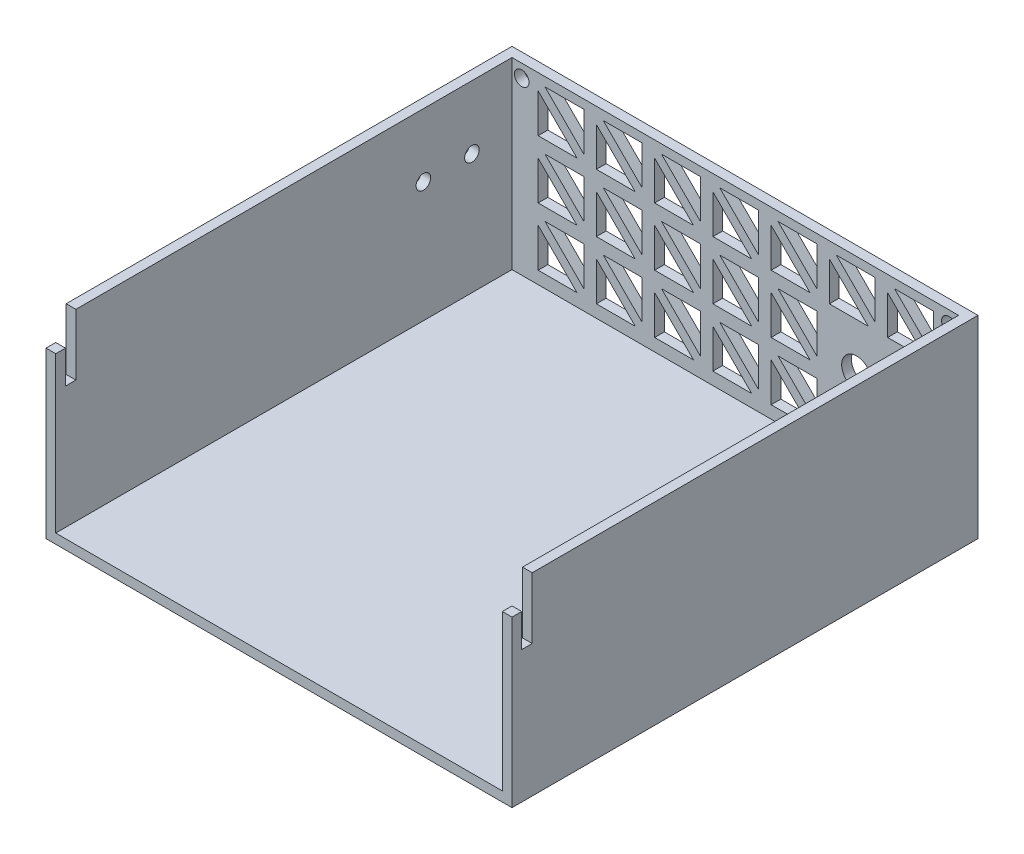
SolidWorks part; units mm, degrees
note: The reader was unsure of these and kept them because the rebuilt part matched: shared geometry of "Sketch7<2>".
ref_plane "Front Plane" through (0, 0, 0) normal (0, 0, 1) x (1, 0, 0)
ref_plane "Top Plane" through (0, 0, 0) normal (0, 1, 0) x (1, 0, 0)
ref_plane "Right Plane" through (0, 0, 0) normal (1, 0, 0) x (0, 0, -1)
sketch "Sketch1" plane through (0, 0, 0) normal (0, 1, 0) x (1, 0, 0)
  line L1 (0, 0) -> (152.4, 0)
  line L2 (0, 0) -> (0, 152.4)
  line L3 (0, 152.4) -> (152.4, 152.4)
  line L4 (152.4, 0) -> (152.4, 152.4)
  dimension "D1" = 152.4
  dimension "D2" = 152.4
extrude "Boss-Extrude1" add sketch "Sketch1" along normal blind 247.65
shell "Shell1" thickness 3.175 removed face at (76.2, 247.65, -76.2) removed face at (76.2, 123.825, 0)
ref_plane "Plane1" through (0, 0, -117.475) normal (0, 0, 1) x (1, 0, 0)
sketch "Sketch3" plane through (0, 0, -117.475) normal (0, 0, 1) x (1, 0, 0)
  line L1 (0, 66.675) -> (152.4, 66.675)
  line L2 (0, 66.675) -> (0, 70.1548)
  line L3 (0, 70.1548) -> (152.4, 70.1548)
  line L4 (152.4, 66.675) -> (152.4, 70.1548)
  line L5 (0, 240.8936) -> (152.4, 240.8936)
  line L6 (3.175, 3.175) -> (149.225, 3.175) construction
  line L8 (0, 195.5546) -> (152.4, 195.5546)
  line L9 (0, 195.5546) -> (0, 192.0748)
  line L10 (0, 192.0748) -> (152.4, 192.0748)
  line L11 (152.4, 195.5546) -> (152.4, 192.0748)
  line L12 (152.4, 247.65) -> (152.4, 0) construction
  line L13 (0, 247.65) -> (0, 0) construction
  line L14 (0, 240.8936) -> (0, 236.8296)
  line L15 (0, 236.8296) -> (152.4, 236.8296)
  line L16 (152.4, 240.8936) -> (152.4, 236.8296)
  dimension "D1" = 3.4798
  dimension "D2" = 63.5
  dimension "D3" = 121.92
  dimension "D4" = 41.275
  dimension "D5" = 4.064
extrude "Cut-Extrude1" cut sketch "Sketch3" along normal up to next
sketch "Sketch4" plane through (152.4, 0, 0) normal (1, 0, 0) x (0, 0, -1)
  line L0 (0, 240.8936) -> (117.475, 240.8936) construction
  line L1 (0, 247.65) -> (6.604, 247.65)
  line L2 (0, 247.65) -> (0, 240.8936)
  line L3 (0, 240.8936) -> (6.604, 240.8936)
  line L4 (6.604, 247.65) -> (6.604, 240.8936)
  line L5 (0, 236.8296) -> (117.475, 236.8296) construction
  line L6 (3.175, 236.8296) -> (6.604, 236.8296)
  line L7 (3.175, 236.8296) -> (3.175, 226.06)
  line L8 (3.175, 226.06) -> (6.604, 226.06)
  line L9 (6.604, 236.8296) -> (6.604, 226.06)
  line L10 (0, 236.8296) -> (0, 195.5546) construction
  line L11 (6.604, 66.675) -> (6.604, 43.2054)
  line L12 (0, 66.675) -> (6.604, 66.675)
  line L13 (0, 66.675) -> (0, 53.975)
  line L14 (0, 53.975) -> (3.175, 53.975)
  line L18 (6.604, 43.2054) -> (3.175, 43.2054)
  line L19 (3.175, 53.975) -> (3.175, 43.2054)
  line L20 (0, 247.65) -> (152.4, 247.65) construction
  line L21 (0, 192.0748) -> (0, 70.1548) construction
  line L23 (3.175, 147.32) -> (3.175, 137.16)
  line L24 (3.175, 137.16) -> (6.604, 137.16)
  line L25 (6.604, 160.528) -> (6.604, 137.16)
  line L28 (3.175, 147.32) -> (0, 147.32)
  line L29 (0, 160.528) -> (0, 147.32)
  line L30 (0, 160.528) -> (6.604, 160.528)
  point P29 (3.175, 231.4448)
  dimension "D1" = 3.175
  dimension "D2" = 3.429
  dimension "D3" = 21.59
  dimension "D4" = 88.9
  dimension "D5" = 12.7
  dimension "D6" = 23.368
  dimension "D7" = 13.208
extrude "Cut-Extrude2" cut sketch "Sketch4" against normal through all
sketch "Sketch5" plane through (0, 0, -152.4) normal (0, 0, -1) x (-1, 0, 0)
  line L0 (-152.4, 0) -> (0, 0) construction
  line L1 (-152.4, 247.65) -> (-152.4, 0) construction
  circle A0 centre (-115.8748, 30.1752) radius 4.8895
  dimension "D1" = 9.779
  dimension "D2" = 30.1752
  dimension "D3" = 36.5252
extrude "Cut-Extrude3" cut sketch "Sketch5" against normal up to next
sketch "Sketch6" plane through (0, 0, -149.225) normal (0, 0, 1) x (1, 0, 0)
  line L0 (140.97, 192.0748) -> (140.97, 179.3748)
  line L1 (140.97, 179.3748) -> (128.27, 192.0748)
  line L2 (128.27, 192.0748) -> (140.97, 192.0748)
  line L3 (149.225, 192.0748) -> (149.225, 160.528) construction
  line L4 (126.0249, 192.0748) -> (140.97, 177.1297) construction
  line L5 (138.7249, 177.1297) -> (126.0249, 189.8297)
  line L6 (126.0249, 177.1297) -> (138.7249, 177.1297)
  line L7 (126.0249, 189.8297) -> (126.0249, 177.1297)
  line L8 (149.225, 192.0748) -> (152.4, 192.0748) construction
  line L9 (140.97, 174.2948) -> (140.97, 161.5948)
  line L10 (140.97, 161.5948) -> (128.27, 174.2948)
  line L11 (128.27, 174.2948) -> (140.97, 174.2948)
  line L12 (138.7249, 159.3497) -> (126.0249, 172.0497)
  line L13 (126.0249, 172.0497) -> (126.0249, 159.3497)
  line L14 (126.0249, 159.3497) -> (138.7249, 159.3497)
  line L15 (140.97, 156.5148) -> (140.97, 143.8148)
  line L16 (140.97, 143.8148) -> (128.27, 156.5148)
  line L17 (128.27, 156.5148) -> (140.97, 156.5148)
  line L18 (138.7249, 141.5697) -> (126.0249, 154.2697)
  line L19 (126.0249, 154.2697) -> (126.0249, 141.5697)
  line L20 (126.0249, 141.5697) -> (138.7249, 141.5697)
  line L21 (140.97, 138.7348) -> (140.97, 126.0348)
  line L22 (140.97, 126.0348) -> (128.27, 138.7348)
  line L23 (128.27, 138.7348) -> (140.97, 138.7348)
  line L24 (138.7249, 123.7897) -> (126.0249, 136.4897)
  line L25 (126.0249, 136.4897) -> (126.0249, 123.7897)
  line L26 (126.0249, 123.7897) -> (138.7249, 123.7897)
  line L27 (140.97, 120.9548) -> (140.97, 108.2548)
  line L28 (140.97, 108.2548) -> (128.27, 120.9548)
  line L29 (128.27, 120.9548) -> (140.97, 120.9548)
  line L30 (138.7249, 106.0097) -> (126.0249, 118.7097)
  line L31 (126.0249, 118.7097) -> (126.0249, 106.0097)
  line L32 (126.0249, 106.0097) -> (138.7249, 106.0097)
  line L33 (140.97, 103.1748) -> (140.97, 90.4748)
  line L34 (140.97, 90.4748) -> (128.27, 103.1748)
  line L35 (128.27, 103.1748) -> (140.97, 103.1748)
  line L36 (138.7249, 88.2297) -> (126.0249, 100.9297)
  line L37 (126.0249, 100.9297) -> (126.0249, 88.2297)
  line L38 (126.0249, 88.2297) -> (138.7249, 88.2297)
  line L39 (140.97, 85.3948) -> (140.97, 72.6948)
  line L40 (140.97, 72.6948) -> (128.27, 85.3948)
  line L41 (128.27, 85.3948) -> (140.97, 85.3948)
  line L42 (138.7249, 70.4497) -> (126.0249, 83.1497)
  line L43 (126.0249, 83.1497) -> (126.0249, 70.4497)
  line L44 (126.0249, 70.4497) -> (138.7249, 70.4497)
  line L45 (121.92, 192.0748) -> (121.92, 179.3748)
  line L46 (121.92, 179.3748) -> (109.22, 192.0748)
  line L47 (109.22, 192.0748) -> (121.92, 192.0748)
  line L48 (119.6749, 177.1297) -> (106.9749, 189.8297)
  line L49 (106.9749, 177.1297) -> (119.6749, 177.1297)
  line L50 (106.9749, 189.8297) -> (106.9749, 177.1297)
  line L51 (121.92, 174.2948) -> (121.92, 161.5948)
  line L52 (121.92, 161.5948) -> (109.22, 174.2948)
  line L53 (109.22, 174.2948) -> (121.92, 174.2948)
  line L54 (119.6749, 159.3497) -> (106.9749, 172.0497)
  line L55 (106.9749, 172.0497) -> (106.9749, 159.3497)
  line L56 (106.9749, 159.3497) -> (119.6749, 159.3497)
  line L57 (121.92, 156.5148) -> (121.92, 143.8148)
  line L58 (121.92, 143.8148) -> (109.22, 156.5148)
  line L59 (109.22, 156.5148) -> (121.92, 156.5148)
  line L60 (119.6749, 141.5697) -> (106.9749, 154.2697)
  line L61 (106.9749, 154.2697) -> (106.9749, 141.5697)
  line L62 (106.9749, 141.5697) -> (119.6749, 141.5697)
  line L63 (121.92, 138.7348) -> (121.92, 126.0348)
  line L64 (121.92, 126.0348) -> (109.22, 138.7348)
  line L65 (109.22, 138.7348) -> (121.92, 138.7348)
  line L66 (119.6749, 123.7897) -> (106.9749, 136.4897)
  line L67 (106.9749, 136.4897) -> (106.9749, 123.7897)
  line L68 (106.9749, 123.7897) -> (119.6749, 123.7897)
  line L69 (121.92, 120.9548) -> (121.92, 108.2548)
  line L70 (121.92, 108.2548) -> (109.22, 120.9548)
  line L71 (109.22, 120.9548) -> (121.92, 120.9548)
  line L72 (119.6749, 106.0097) -> (106.9749, 118.7097)
  line L73 (106.9749, 118.7097) -> (106.9749, 106.0097)
  line L74 (106.9749, 106.0097) -> (119.6749, 106.0097)
  line L75 (121.92, 103.1748) -> (121.92, 90.4748)
  line L76 (121.92, 90.4748) -> (109.22, 103.1748)
  line L77 (109.22, 103.1748) -> (121.92, 103.1748)
  line L78 (119.6749, 88.2297) -> (106.9749, 100.9297)
  line L79 (106.9749, 100.9297) -> (106.9749, 88.2297)
  line L80 (106.9749, 88.2297) -> (119.6749, 88.2297)
  line L81 (121.92, 85.3948) -> (121.92, 72.6948)
  line L82 (121.92, 72.6948) -> (109.22, 85.3948)
  line L83 (109.22, 85.3948) -> (121.92, 85.3948)
  line L84 (119.6749, 70.4497) -> (106.9749, 83.1497)
  line L85 (106.9749, 83.1497) -> (106.9749, 70.4497)
  line L86 (106.9749, 70.4497) -> (119.6749, 70.4497)
  line L87 (102.87, 192.0748) -> (102.87, 179.3748)
  line L88 (102.87, 179.3748) -> (90.17, 192.0748)
  line L89 (90.17, 192.0748) -> (102.87, 192.0748)
  line L90 (100.6249, 177.1297) -> (87.9249, 189.8297)
  line L91 (87.9249, 177.1297) -> (100.6249, 177.1297)
  line L92 (87.9249, 189.8297) -> (87.9249, 177.1297)
  line L93 (102.87, 174.2948) -> (102.87, 161.5948)
  line L94 (102.87, 161.5948) -> (90.17, 174.2948)
  line L95 (90.17, 174.2948) -> (102.87, 174.2948)
  line L96 (100.6249, 159.3497) -> (87.9249, 172.0497)
  line L97 (87.9249, 172.0497) -> (87.9249, 159.3497)
  line L98 (87.9249, 159.3497) -> (100.6249, 159.3497)
  line L99 (102.87, 156.5148) -> (102.87, 143.8148)
  line L100 (102.87, 143.8148) -> (90.17, 156.5148)
  line L101 (90.17, 156.5148) -> (102.87, 156.5148)
  line L102 (100.6249, 141.5697) -> (87.9249, 154.2697)
  line L103 (87.9249, 154.2697) -> (87.9249, 141.5697)
  line L104 (87.9249, 141.5697) -> (100.6249, 141.5697)
  line L105 (102.87, 138.7348) -> (102.87, 126.0348)
  line L106 (102.87, 126.0348) -> (90.17, 138.7348)
  line L107 (90.17, 138.7348) -> (102.87, 138.7348)
  line L108 (100.6249, 123.7897) -> (87.9249, 136.4897)
  line L109 (87.9249, 136.4897) -> (87.9249, 123.7897)
  line L110 (87.9249, 123.7897) -> (100.6249, 123.7897)
  line L111 (102.87, 120.9548) -> (102.87, 108.2548)
  line L112 (102.87, 108.2548) -> (90.17, 120.9548)
  line L113 (90.17, 120.9548) -> (102.87, 120.9548)
  line L114 (100.6249, 106.0097) -> (87.9249, 118.7097)
  line L115 (87.9249, 118.7097) -> (87.9249, 106.0097)
  line L116 (87.9249, 106.0097) -> (100.6249, 106.0097)
  line L117 (102.87, 103.1748) -> (102.87, 90.4748)
  line L118 (102.87, 90.4748) -> (90.17, 103.1748)
  line L119 (90.17, 103.1748) -> (102.87, 103.1748)
  line L120 (100.6249, 88.2297) -> (87.9249, 100.9297)
  line L121 (87.9249, 100.9297) -> (87.9249, 88.2297)
  line L122 (87.9249, 88.2297) -> (100.6249, 88.2297)
  line L123 (102.87, 85.3948) -> (102.87, 72.6948)
  line L124 (102.87, 72.6948) -> (90.17, 85.3948)
  line L125 (90.17, 85.3948) -> (102.87, 85.3948)
  line L126 (100.6249, 70.4497) -> (87.9249, 83.1497)
  line L127 (87.9249, 83.1497) -> (87.9249, 70.4497)
  line L128 (87.9249, 70.4497) -> (100.6249, 70.4497)
  line L129 (83.82, 192.0748) -> (83.82, 179.3748)
  line L130 (83.82, 179.3748) -> (71.12, 192.0748)
  line L131 (71.12, 192.0748) -> (83.82, 192.0748)
  line L132 (81.5749, 177.1297) -> (68.8749, 189.8297)
  line L133 (68.8749, 177.1297) -> (81.5749, 177.1297)
  line L134 (68.8749, 189.8297) -> (68.8749, 177.1297)
  line L135 (83.82, 174.2948) -> (83.82, 161.5948)
  line L136 (83.82, 161.5948) -> (71.12, 174.2948)
  line L137 (71.12, 174.2948) -> (83.82, 174.2948)
  line L138 (81.5749, 159.3497) -> (68.8749, 172.0497)
  line L139 (68.8749, 172.0497) -> (68.8749, 159.3497)
  line L140 (68.8749, 159.3497) -> (81.5749, 159.3497)
  line L141 (83.82, 156.5148) -> (83.82, 143.8148)
  line L142 (83.82, 143.8148) -> (71.12, 156.5148)
  line L143 (71.12, 156.5148) -> (83.82, 156.5148)
  line L144 (81.5749, 141.5697) -> (68.8749, 154.2697)
  line L145 (68.8749, 154.2697) -> (68.8749, 141.5697)
  line L146 (68.8749, 141.5697) -> (81.5749, 141.5697)
  line L147 (83.82, 138.7348) -> (83.82, 126.0348)
  line L148 (83.82, 126.0348) -> (71.12, 138.7348)
  line L149 (71.12, 138.7348) -> (83.82, 138.7348)
  line L150 (81.5749, 123.7897) -> (68.8749, 136.4897)
  line L151 (68.8749, 136.4897) -> (68.8749, 123.7897)
  line L152 (68.8749, 123.7897) -> (81.5749, 123.7897)
  line L153 (83.82, 120.9548) -> (83.82, 108.2548)
  line L154 (83.82, 108.2548) -> (71.12, 120.9548)
  line L155 (71.12, 120.9548) -> (83.82, 120.9548)
  line L156 (81.5749, 106.0097) -> (68.8749, 118.7097)
  line L157 (68.8749, 118.7097) -> (68.8749, 106.0097)
  line L158 (68.8749, 106.0097) -> (81.5749, 106.0097)
  line L159 (83.82, 103.1748) -> (83.82, 90.4748)
  line L160 (83.82, 90.4748) -> (71.12, 103.1748)
  line L161 (71.12, 103.1748) -> (83.82, 103.1748)
  line L162 (81.5749, 88.2297) -> (68.8749, 100.9297)
  line L163 (68.8749, 100.9297) -> (68.8749, 88.2297)
  line L164 (68.8749, 88.2297) -> (81.5749, 88.2297)
  line L165 (83.82, 85.3948) -> (83.82, 72.6948)
  line L166 (83.82, 72.6948) -> (71.12, 85.3948)
  line L167 (71.12, 85.3948) -> (83.82, 85.3948)
  line L168 (81.5749, 70.4497) -> (68.8749, 83.1497)
  line L169 (68.8749, 83.1497) -> (68.8749, 70.4497)
  line L170 (68.8749, 70.4497) -> (81.5749, 70.4497)
  line L171 (64.77, 192.0748) -> (64.77, 179.3748)
  line L172 (64.77, 179.3748) -> (52.07, 192.0748)
  line L173 (52.07, 192.0748) -> (64.77, 192.0748)
  line L174 (62.5249, 177.1297) -> (49.8249, 189.8297)
  line L175 (49.8249, 177.1297) -> (62.5249, 177.1297)
  line L176 (49.8249, 189.8297) -> (49.8249, 177.1297)
  line L177 (64.77, 174.2948) -> (64.77, 161.5948)
  line L178 (64.77, 161.5948) -> (52.07, 174.2948)
  line L179 (52.07, 174.2948) -> (64.77, 174.2948)
  line L180 (62.5249, 159.3497) -> (49.8249, 172.0497)
  line L181 (49.8249, 172.0497) -> (49.8249, 159.3497)
  line L182 (49.8249, 159.3497) -> (62.5249, 159.3497)
  line L183 (64.77, 156.5148) -> (64.77, 143.8148)
  line L184 (64.77, 143.8148) -> (52.07, 156.5148)
  line L185 (52.07, 156.5148) -> (64.77, 156.5148)
  line L186 (62.5249, 141.5697) -> (49.8249, 154.2697)
  line L187 (49.8249, 154.2697) -> (49.8249, 141.5697)
  line L188 (49.8249, 141.5697) -> (62.5249, 141.5697)
  line L189 (64.77, 138.7348) -> (64.77, 126.0348)
  line L190 (64.77, 126.0348) -> (52.07, 138.7348)
  line L191 (52.07, 138.7348) -> (64.77, 138.7348)
  line L192 (62.5249, 123.7897) -> (49.8249, 136.4897)
  line L193 (49.8249, 136.4897) -> (49.8249, 123.7897)
  line L194 (49.8249, 123.7897) -> (62.5249, 123.7897)
  line L195 (64.77, 120.9548) -> (64.77, 108.2548)
  line L196 (64.77, 108.2548) -> (52.07, 120.9548)
  line L197 (52.07, 120.9548) -> (64.77, 120.9548)
  line L198 (62.5249, 106.0097) -> (49.8249, 118.7097)
  line L199 (49.8249, 118.7097) -> (49.8249, 106.0097)
  line L200 (49.8249, 106.0097) -> (62.5249, 106.0097)
  line L201 (64.77, 103.1748) -> (64.77, 90.4748)
  line L202 (64.77, 90.4748) -> (52.07, 103.1748)
  line L203 (52.07, 103.1748) -> (64.77, 103.1748)
  line L204 (62.5249, 88.2297) -> (49.8249, 100.9297)
  line L205 (49.8249, 100.9297) -> (49.8249, 88.2297)
  line L206 (49.8249, 88.2297) -> (62.5249, 88.2297)
  line L207 (64.77, 85.3948) -> (64.77, 72.6948)
  line L208 (64.77, 72.6948) -> (52.07, 85.3948)
  line L209 (52.07, 85.3948) -> (64.77, 85.3948)
  line L210 (62.5249, 70.4497) -> (49.8249, 83.1497)
  line L211 (49.8249, 83.1497) -> (49.8249, 70.4497)
  line L212 (49.8249, 70.4497) -> (62.5249, 70.4497)
  line L213 (45.72, 192.0748) -> (45.72, 179.3748)
  line L214 (45.72, 179.3748) -> (33.02, 192.0748)
  line L215 (33.02, 192.0748) -> (45.72, 192.0748)
  line L216 (43.4749, 177.1297) -> (30.7749, 189.8297)
  line L217 (30.7749, 177.1297) -> (43.4749, 177.1297)
  line L218 (30.7749, 189.8297) -> (30.7749, 177.1297)
  line L219 (45.72, 174.2948) -> (45.72, 161.5948)
  line L220 (45.72, 161.5948) -> (33.02, 174.2948)
  line L221 (33.02, 174.2948) -> (45.72, 174.2948)
  line L222 (43.4749, 159.3497) -> (30.7749, 172.0497)
  line L223 (30.7749, 172.0497) -> (30.7749, 159.3497)
  line L224 (30.7749, 159.3497) -> (43.4749, 159.3497)
  line L225 (45.72, 156.5148) -> (45.72, 143.8148)
  line L226 (45.72, 143.8148) -> (33.02, 156.5148)
  line L227 (33.02, 156.5148) -> (45.72, 156.5148)
  line L228 (43.4749, 141.5697) -> (30.7749, 154.2697)
  line L229 (30.7749, 154.2697) -> (30.7749, 141.5697)
  line L230 (30.7749, 141.5697) -> (43.4749, 141.5697)
  line L231 (45.72, 138.7348) -> (45.72, 126.0348)
  line L232 (45.72, 126.0348) -> (33.02, 138.7348)
  line L233 (33.02, 138.7348) -> (45.72, 138.7348)
  line L234 (43.4749, 123.7897) -> (30.7749, 136.4897)
  line L235 (30.7749, 136.4897) -> (30.7749, 123.7897)
  line L236 (30.7749, 123.7897) -> (43.4749, 123.7897)
  line L237 (45.72, 120.9548) -> (45.72, 108.2548)
  line L238 (45.72, 108.2548) -> (33.02, 120.9548)
  line L239 (33.02, 120.9548) -> (45.72, 120.9548)
  line L240 (43.4749, 106.0097) -> (30.7749, 118.7097)
  line L241 (30.7749, 118.7097) -> (30.7749, 106.0097)
  line L242 (30.7749, 106.0097) -> (43.4749, 106.0097)
  line L243 (45.72, 103.1748) -> (45.72, 90.4748)
  line L244 (45.72, 90.4748) -> (33.02, 103.1748)
  line L245 (33.02, 103.1748) -> (45.72, 103.1748)
  line L246 (43.4749, 88.2297) -> (30.7749, 100.9297)
  line L247 (30.7749, 100.9297) -> (30.7749, 88.2297)
  line L248 (30.7749, 88.2297) -> (43.4749, 88.2297)
  line L249 (45.72, 85.3948) -> (45.72, 72.6948)
  line L250 (45.72, 72.6948) -> (33.02, 85.3948)
  line L251 (33.02, 85.3948) -> (45.72, 85.3948)
  line L252 (43.4749, 70.4497) -> (30.7749, 83.1497)
  line L253 (30.7749, 83.1497) -> (30.7749, 70.4497)
  line L254 (30.7749, 70.4497) -> (43.4749, 70.4497)
  line L255 (26.67, 192.0748) -> (26.67, 179.3748)
  line L256 (26.67, 179.3748) -> (13.97, 192.0748)
  line L257 (13.97, 192.0748) -> (26.67, 192.0748)
  line L258 (24.4249, 177.1297) -> (11.7249, 189.8297)
  line L259 (11.7249, 177.1297) -> (24.4249, 177.1297)
  line L260 (11.7249, 189.8297) -> (11.7249, 177.1297)
  line L261 (26.67, 174.2948) -> (26.67, 161.5948)
  line L262 (26.67, 161.5948) -> (13.97, 174.2948)
  line L263 (13.97, 174.2948) -> (26.67, 174.2948)
  line L264 (24.4249, 159.3497) -> (11.7249, 172.0497)
  line L265 (11.7249, 172.0497) -> (11.7249, 159.3497)
  line L266 (11.7249, 159.3497) -> (24.4249, 159.3497)
  line L267 (26.67, 156.5148) -> (26.67, 143.8148)
  line L268 (26.67, 143.8148) -> (13.97, 156.5148)
  line L269 (13.97, 156.5148) -> (26.67, 156.5148)
  line L270 (24.4249, 141.5697) -> (11.7249, 154.2697)
  line L271 (11.7249, 154.2697) -> (11.7249, 141.5697)
  line L272 (11.7249, 141.5697) -> (24.4249, 141.5697)
  line L273 (26.67, 138.7348) -> (26.67, 126.0348)
  line L274 (26.67, 126.0348) -> (13.97, 138.7348)
  line L275 (13.97, 138.7348) -> (26.67, 138.7348)
  line L276 (24.4249, 123.7897) -> (11.7249, 136.4897)
  line L277 (11.7249, 136.4897) -> (11.7249, 123.7897)
  line L278 (11.7249, 123.7897) -> (24.4249, 123.7897)
  line L279 (26.67, 120.9548) -> (26.67, 108.2548)
  line L280 (26.67, 108.2548) -> (13.97, 120.9548)
  line L281 (13.97, 120.9548) -> (26.67, 120.9548)
  line L282 (24.4249, 106.0097) -> (11.7249, 118.7097)
  line L283 (11.7249, 118.7097) -> (11.7249, 106.0097)
  line L284 (11.7249, 106.0097) -> (24.4249, 106.0097)
  line L285 (26.67, 103.1748) -> (26.67, 90.4748)
  line L286 (26.67, 90.4748) -> (13.97, 103.1748)
  line L287 (13.97, 103.1748) -> (26.67, 103.1748)
  line L288 (24.4249, 88.2297) -> (11.7249, 100.9297)
  line L289 (11.7249, 100.9297) -> (11.7249, 88.2297)
  line L290 (11.7249, 88.2297) -> (24.4249, 88.2297)
  line L291 (26.67, 85.3948) -> (26.67, 72.6948)
  line L292 (26.67, 72.6948) -> (13.97, 85.3948)
  line L293 (13.97, 85.3948) -> (26.67, 85.3948)
  line L294 (24.4249, 70.4497) -> (11.7249, 83.1497)
  line L295 (11.7249, 83.1497) -> (11.7249, 70.4497)
  line L296 (11.7249, 70.4497) -> (24.4249, 70.4497)
  line L297 (149.225, 60.325) -> (3.175, 60.325) construction
  line L298 (149.225, 247.65) -> (149.225, 3.175) construction
  line L299 (3.175, 43.2054) -> (3.175, 66.675) construction
  line L300 (149.225, 3.175) -> (3.175, 3.175) construction
  line L301 (140.97, 60.325) -> (140.97, 47.625)
  line L302 (140.97, 47.625) -> (128.27, 60.325)
  line L303 (128.27, 60.325) -> (140.97, 60.325)
  line L304 (126.0249, 60.325) -> (147.432, 38.918) construction
  line L305 (126.0249, 58.0799) -> (126.0249, 45.3799)
  line L306 (138.7249, 45.3799) -> (126.0249, 58.0799)
  line L307 (126.0249, 45.3799) -> (138.7249, 45.3799)
  line L308 (121.92, 60.325) -> (121.92, 47.625)
  line L309 (121.92, 47.625) -> (109.22, 60.325)
  line L310 (109.22, 60.325) -> (121.92, 60.325)
  line L311 (106.9749, 58.0799) -> (106.9749, 45.3799)
  line L312 (119.6749, 45.3799) -> (106.9749, 58.0799)
  line L313 (106.9749, 45.3799) -> (119.6749, 45.3799)
  line L314 (102.87, 60.325) -> (102.87, 47.625)
  line L315 (102.87, 47.625) -> (90.17, 60.325)
  line L316 (90.17, 60.325) -> (102.87, 60.325)
  line L317 (87.9249, 58.0799) -> (87.9249, 45.3799)
  line L318 (100.6249, 45.3799) -> (87.9249, 58.0799)
  line L319 (87.9249, 45.3799) -> (100.6249, 45.3799)
  line L320 (83.82, 60.325) -> (83.82, 47.625)
  line L321 (83.82, 47.625) -> (71.12, 60.325)
  line L322 (71.12, 60.325) -> (83.82, 60.325)
  line L323 (68.8749, 58.0799) -> (68.8749, 45.3799)
  line L324 (81.5749, 45.3799) -> (68.8749, 58.0799)
  line L325 (68.8749, 45.3799) -> (81.5749, 45.3799)
  line L326 (64.77, 60.325) -> (64.77, 47.625)
  line L327 (64.77, 47.625) -> (52.07, 60.325)
  line L328 (52.07, 60.325) -> (64.77, 60.325)
  line L329 (49.8249, 58.0799) -> (49.8249, 45.3799)
  line L330 (62.5249, 45.3799) -> (49.8249, 58.0799)
  line L331 (49.8249, 45.3799) -> (62.5249, 45.3799)
  line L332 (45.72, 60.325) -> (45.72, 47.625)
  line L333 (45.72, 47.625) -> (33.02, 60.325)
  line L334 (33.02, 60.325) -> (45.72, 60.325)
  line L335 (30.7749, 58.0799) -> (30.7749, 45.3799)
  line L336 (43.4749, 45.3799) -> (30.7749, 58.0799)
  line L337 (30.7749, 45.3799) -> (43.4749, 45.3799)
  line L338 (26.67, 60.325) -> (26.67, 47.625)
  line L339 (26.67, 47.625) -> (13.97, 60.325)
  line L340 (13.97, 60.325) -> (26.67, 60.325)
  line L341 (11.7249, 58.0799) -> (11.7249, 45.3799)
  line L342 (24.4249, 45.3799) -> (11.7249, 58.0799)
  line L343 (11.7249, 45.3799) -> (24.4249, 45.3799)
  line L344 (102.87, 41.275) -> (102.87, 28.575)
  line L345 (102.87, 28.575) -> (90.17, 41.275)
  line L346 (90.17, 41.275) -> (102.87, 41.275)
  line L347 (87.9249, 39.0299) -> (87.9249, 26.3299)
  line L348 (100.6249, 26.3299) -> (87.9249, 39.0299)
  line L349 (87.9249, 26.3299) -> (100.6249, 26.3299)
  line L350 (83.82, 41.275) -> (83.82, 28.575)
  line L351 (83.82, 28.575) -> (71.12, 41.275)
  line L352 (71.12, 41.275) -> (83.82, 41.275)
  line L353 (68.8749, 39.0299) -> (68.8749, 26.3299)
  line L354 (81.5749, 26.3299) -> (68.8749, 39.0299)
  line L355 (68.8749, 26.3299) -> (81.5749, 26.3299)
  line L356 (64.77, 41.275) -> (64.77, 28.575)
  line L357 (64.77, 28.575) -> (52.07, 41.275)
  line L358 (52.07, 41.275) -> (64.77, 41.275)
  line L359 (49.8249, 39.0299) -> (49.8249, 26.3299)
  line L360 (62.5249, 26.3299) -> (49.8249, 39.0299)
  line L361 (49.8249, 26.3299) -> (62.5249, 26.3299)
  line L362 (45.72, 41.275) -> (45.72, 28.575)
  line L363 (45.72, 28.575) -> (33.02, 41.275)
  line L364 (33.02, 41.275) -> (45.72, 41.275)
  line L365 (30.7749, 39.0299) -> (30.7749, 26.3299)
  line L366 (43.4749, 26.3299) -> (30.7749, 39.0299)
  line L367 (30.7749, 26.3299) -> (43.4749, 26.3299)
  line L368 (26.67, 41.275) -> (26.67, 28.575)
  line L369 (26.67, 28.575) -> (13.97, 41.275)
  line L370 (13.97, 41.275) -> (26.67, 41.275)
  line L371 (11.7249, 39.0299) -> (11.7249, 26.3299)
  line L372 (24.4249, 26.3299) -> (11.7249, 39.0299)
  line L373 (11.7249, 26.3299) -> (24.4249, 26.3299)
  line L374 (126.0249, 26.3299) -> (138.7249, 26.3299)
  line L375 (126.0249, 39.0299) -> (126.0249, 26.3299)
  line L376 (138.7249, 26.3299) -> (126.0249, 39.0299)
  line L377 (140.97, 28.575) -> (128.27, 41.275)
  line L378 (128.27, 41.275) -> (140.97, 41.275)
  line L379 (140.97, 41.275) -> (140.97, 28.575)
  line L380 (102.87, 22.225) -> (102.87, 9.525)
  line L381 (102.87, 9.525) -> (90.17, 22.225)
  line L382 (90.17, 22.225) -> (102.87, 22.225)
  line L383 (87.9249, 19.9799) -> (87.9249, 7.2799)
  line L384 (100.6249, 7.2799) -> (87.9249, 19.9799)
  line L385 (87.9249, 7.2799) -> (100.6249, 7.2799)
  line L386 (83.82, 22.225) -> (83.82, 9.525)
  line L387 (83.82, 9.525) -> (71.12, 22.225)
  line L388 (71.12, 22.225) -> (83.82, 22.225)
  line L389 (68.8749, 19.9799) -> (68.8749, 7.2799)
  line L390 (81.5749, 7.2799) -> (68.8749, 19.9799)
  line L391 (68.8749, 7.2799) -> (81.5749, 7.2799)
  line L392 (64.77, 22.225) -> (64.77, 9.525)
  line L393 (64.77, 9.525) -> (52.07, 22.225)
  line L394 (52.07, 22.225) -> (64.77, 22.225)
  line L395 (49.8249, 19.9799) -> (49.8249, 7.2799)
  line L396 (62.5249, 7.2799) -> (49.8249, 19.9799)
  line L397 (49.8249, 7.2799) -> (62.5249, 7.2799)
  line L398 (45.72, 22.225) -> (45.72, 9.525)
  line L399 (45.72, 9.525) -> (33.02, 22.225)
  line L400 (33.02, 22.225) -> (45.72, 22.225)
  line L401 (30.7749, 19.9799) -> (30.7749, 7.2799)
  line L402 (43.4749, 7.2799) -> (30.7749, 19.9799)
  line L403 (30.7749, 7.2799) -> (43.4749, 7.2799)
  line L404 (26.67, 22.225) -> (26.67, 9.525)
  line L405 (26.67, 9.525) -> (13.97, 22.225)
  line L406 (13.97, 22.225) -> (26.67, 22.225)
  line L407 (11.7249, 19.9799) -> (11.7249, 7.2799)
  line L408 (24.4249, 7.2799) -> (11.7249, 19.9799)
  line L409 (11.7249, 7.2799) -> (24.4249, 7.2799)
  line L410 (126.0249, 7.2799) -> (138.7249, 7.2799)
  line L411 (126.0249, 19.9799) -> (126.0249, 7.2799)
  line L412 (138.7249, 7.2799) -> (126.0249, 19.9799)
  line L413 (140.97, 9.525) -> (128.27, 22.225)
  line L414 (128.27, 22.225) -> (140.97, 22.225)
  line L415 (140.97, 22.225) -> (140.97, 9.525)
  dimension "D1" = 8.255
  dimension "D2" = 12.7
  dimension "D3" = 1.5875
  dimension "D4" = 7
  dimension "D6" = 57.15
  dimension "D7" = 1.5875
  dimension "D5" = 7
  dimension "D8" = 7
  dimension "D9" = 3
extrude "Cut-Extrude4" cut sketch "Sketch6" against normal up to next (3.175 mm away)
sketch "Sketch7" plane through (0, 0, 0) normal (-1, 0, 0) x (0, 0, 1)
  line L1 (0, 195.5546) -> (-117.475, 195.5546) construction
  line L2 (0, 70.1548) -> (-117.475, 70.1548) construction
  line L3 (0, 192.0748) -> (0, 160.528) construction
  circle A0 centre (-136.111, 217.7796) radius 2.3813
  circle A1 centre (-120.236, 217.7796) radius 2.3813
  circle A2 centre (-136.111, 159.3596) radius 2.3813
  circle A3 centre (-120.236, 159.3596) radius 2.3813
  circle A4 centre (-136.111, 100.9396) radius 2.3813
  circle A5 centre (-120.236, 100.9396) radius 2.3813
  circle A6 centre (-136.111, 42.5196) radius 2.3813
  circle A7 centre (-120.236, 42.5196) radius 2.3813
  circle A8 centre (-15.875, 183.1848) radius 2.3813
  circle A9 centre (-15.875, 175.5648) radius 2.3813
  circle A10 centre (-15.875, 78.4098) radius 2.3812
  circle A11 centre (-15.875, 86.0298) radius 2.3812
  dimension "D1" = 4.7625
  dimension "D2" = 113.03
  dimension "D3" = 15.875
  dimension "D4" = 22.225
  dimension "D6" = 7.62
  dimension "D8" = 15.875
  dimension "D5" = 4
  dimension "D7" = 2
extrude "Cut-Extrude5" cut sketch "Sketch7" against normal up to next
extrude "Cut-Extrude6" cut sketch "Sketch7<2>" against normal through all contours A8 | A9 | A11 | A10
sketch "Sketch7<2>" plane through (0, 0, 0) normal (-1, 0, 0) x (0, 0, 1) same geometry as "Sketch7"
sketch "Sketch8" plane through (0, 0, -149.225) normal (0, 0, 1) x (1, 0, 0)
  line L0 (0, 63.754) -> (152.4, 63.754) construction
  line L1 (0, 43.2054) -> (0, 66.675) construction
  line L2 (152.4, 43.2054) -> (152.4, 66.675) construction
  line L3 (149.225, 247.65) -> (3.175, 247.65) construction
  line L4 (3.175, 43.2054) -> (3.175, 66.675) construction
  line L9 (76.2, 3.175) -> (76.2, 63.754) construction
  line L10 (149.225, 3.175) -> (3.175, 3.175) construction
  circle A0 centre (6.35, 68.5165) radius 2.3812
  circle A1 centre (6.35, 58.9915) radius 2.3812
  circle A2 centre (146.05, 58.9915) radius 2.3813
  circle A3 centre (146.05, 68.5165) radius 2.3813
  dimension "D3" = 4.7625
  dimension "D1" = 183.896
  dimension "D2" = 9.525
  dimension "D4" = 4.7625
  dimension "D5" = 3.175
extrude "Cut-Extrude8" cut sketch "Sketch8" against normal through all
sketch "Sketch9" plane through (0, 0, 0) normal (0, 0, 1) x (1, 0, 0)
  line L0 (0, 63.246) -> (152.4, 63.246) construction
  line L4 (149.225, 247.65) -> (3.175, 247.65) construction
  line L6 (-34.5376, 252.8017) -> (152.4, 252.8017)
  line L7 (-34.5376, 252.8017) -> (-34.5376, 63.246)
  line L8 (-34.5376, 63.246) -> (152.4, 63.246)
  line L9 (152.4, 252.8017) -> (152.4, 63.246)
  dimension "D1" = 184.404
extrude "Cut-Extrude9" cut sketch "Sketch9" against normal through all
